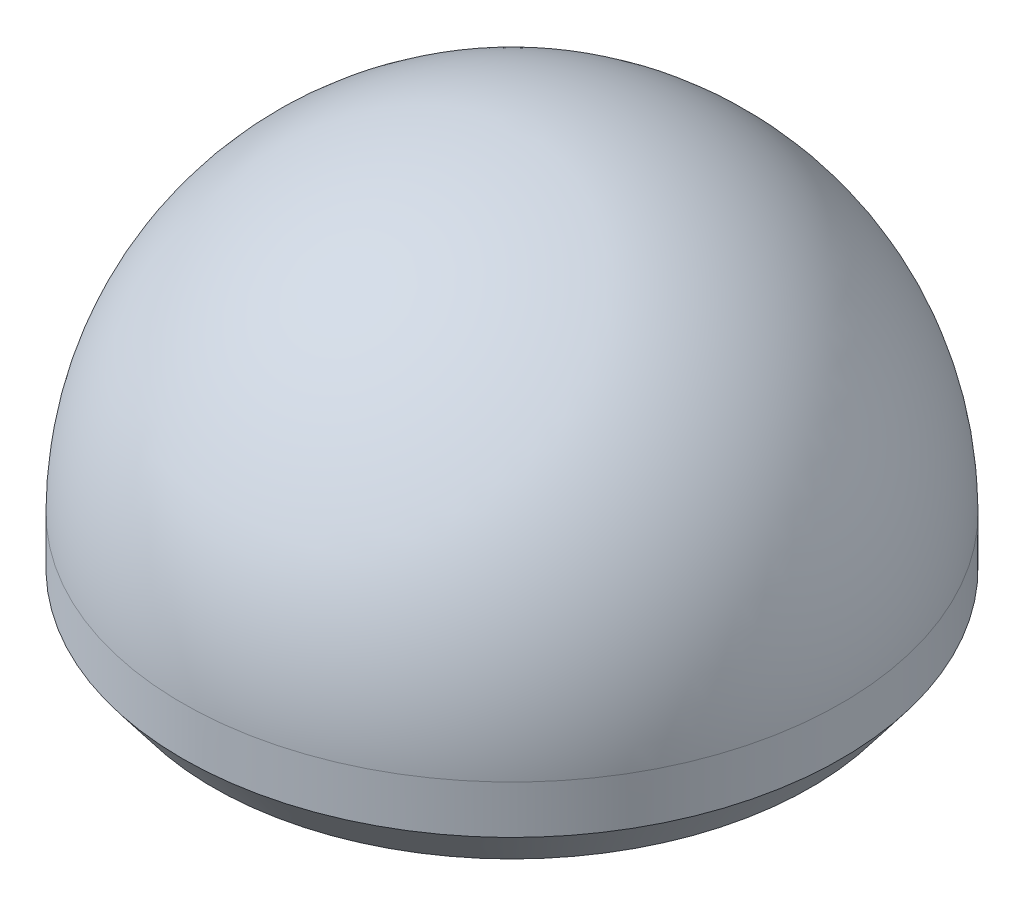
SolidWorks part; units mm, degrees
ref_plane "Front Plane" through (0, 0, 0) normal (0, 0, 1) x (1, 0, 0)
ref_plane "Top Plane" through (0, 0, 0) normal (0, 1, 0) x (1, 0, 0)
ref_plane "Right Plane" through (0, 0, 0) normal (1, 0, 0) x (0, 0, -1)
sketch "Sketch1" plane through (0, 0, 0) normal (0, 0, 1) x (1, 0, 0)
  line L0 (-150, 0) -> (-150, -21.8397)
  line L1 (-150, -21.8397) -> (-135.9926, -40.2239)
  line L3 (0, 0) -> (0, 150)
  arc A0 (0, 150) -> (-150, 0) centre (0, 0) ccw
  arc A2 (0, 0) -> (-135.9926, -40.2239) centre (0, -250) ccw
  dimension "D1" = 300
  dimension "D2" = 500
revolve "Revolve1" add sketch "Sketch1" angle 360 about L3
sketch "Sketch2" plane through (0, 0, 0) normal (0, 0, 1) x (1, 0, 0)
  line L1 (88.9252, -25.6799) -> (88.9252, 14.3201)
  arc A0 (135.9926, -40.2239) -> (-135.9926, -40.2239) centre (0, -250) ccw
  arc A1 (88.9252, -25.6799) -> (88.9252, 14.3201) centre (88.9252, -5.6799) ccw
  dimension "D2" = 500
  dimension "D3" = 20
  dimension "D1" = 40
  dimension "D4" = 260
sketch "Sketch3" plane through (0, 0, 0) normal (0, 0, 1) x (1, 0, 0)
  line L0 (0, -45.0192) -> (0, 68.2874)
revolve "Cut-Revolve2" cut sketch "Sketch2" angle 360 about L1
pattern_circular "CirPattern2" count 4 over 360 about axis through (0, -45.0192, 0) along (0, 1, 0) of "Cut-Revolve2"
sketch "Sketch8" [suppressed] plane through (0, 0, 0) normal (1, 0, 0) x (0, 0, -1)
  line L0 (-87.0412, 0) -> (-39.0742, 131.7881)
  dimension "D1" = 70
ref_plane "Plane2" [suppressed] through (0, 27.9745, 76.8593) normal (0, -0.342, -0.9397) x (0, 0.9397, -0.342)
ref_plane "Plane3" [suppressed] through (0, 50.2058, 137.9393) normal (0, -0.342, -0.9397) x (0, 0.9397, -0.342)
sketch "Sketch10" [suppressed] plane through (0, 50.2058, 137.9393) normal (0, -0.342, -0.9397) x (0, 0.9397, -0.342)
  line L0 (14.9253, -20) -> (14.9253, 20)
  line L3 (9.9253, -20) -> (9.9253, 20)
  line L4 (8.9253, -20) -> (8.9253, 20)
  line L5 (15.9253, -20) -> (15.9253, 20)
  line L6 (14.9253, 20) -> (14.5296, 20.0088)
  line L7 (-29.7698, 0) -> (110.4762, 0) construction
  line L8 (20.9253, -20) -> (20.9253, 20)
  line L9 (3.9253, -20) -> (3.9253, 20)
  line L10 (21.9253, -20) -> (21.9253, 20)
  line L11 (2.9253, -20) -> (2.9253, 20)
  arc A0 (9.9253, -20) -> (14.9253, -20) centre (12.4253, -20) ccw
  arc A1 (14.9253, 20) -> (9.9253, 20) centre (12.4253, 20) ccw
  arc A2 (15.9253, 20) -> (8.9253, 20) centre (12.4253, 20) ccw
  arc A3 (8.9253, -20) -> (15.9253, -20) centre (12.4253, -20) ccw
  arc A4 (3.9253, -20) -> (20.9253, -20) centre (12.4253, -20) ccw
  arc A5 (20.9253, 20) -> (3.9253, 20) centre (12.4253, 20) ccw
  arc A6 (2.9253, -20) -> (21.9253, -20) centre (12.4253, -20) ccw
  arc A7 (21.9253, 20) -> (2.9253, 20) centre (12.4253, 20) ccw
  dimension "D1" = 5
  dimension "D2" = 40
  dimension "D3" = 20
  dimension "D4" = 1
  dimension "D5" = 5
  dimension "D6" = 1
extrude "Boss-Extrude3" [suppressed] add sketch "Sketch10" against normal blind 10
